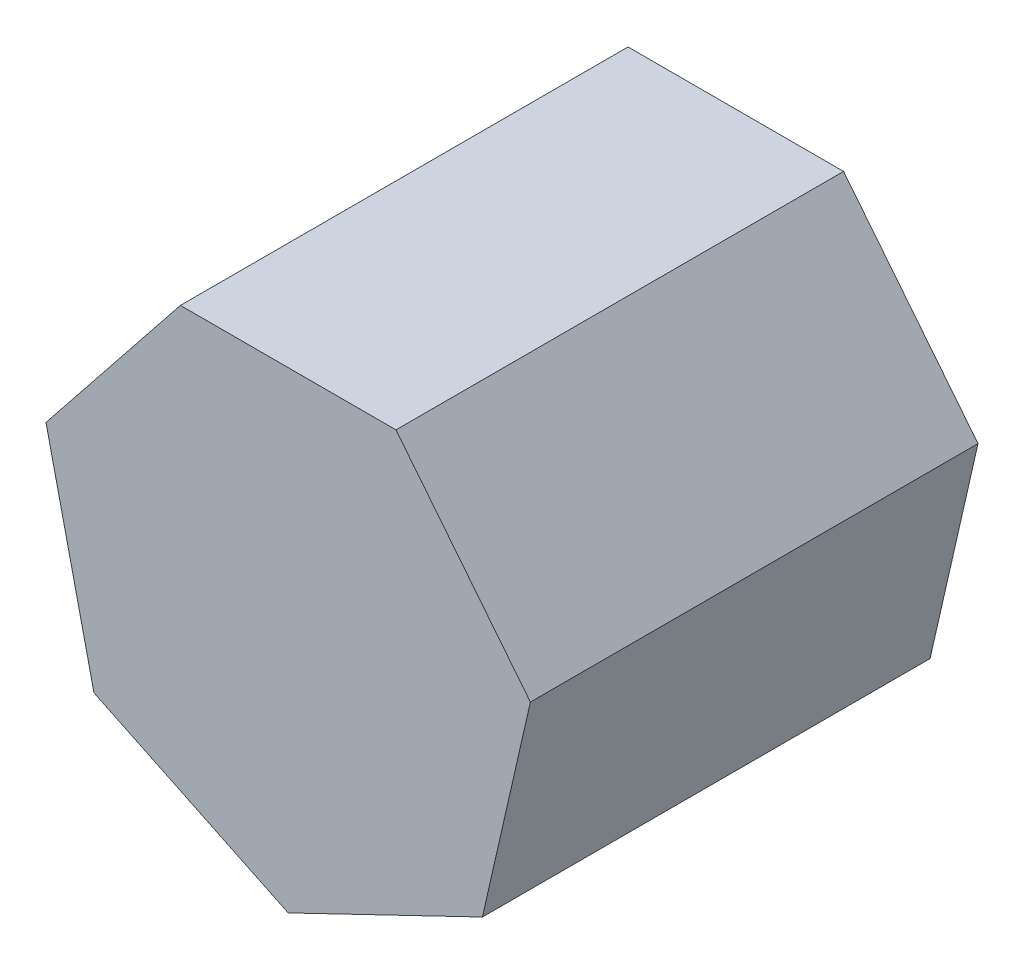
SolidWorks part; units mm, degrees
ref_plane "Front Plane" through (0, 0, 0) normal (0, 0, 1) x (1, 0, 0)
ref_plane "Top Plane" through (0, 0, 0) normal (0, 1, 0) x (1, 0, 0)
ref_plane "Right Plane" through (0, 0, 0) normal (1, 0, 0) x (0, 0, -1)
sketch "Sketch1" plane through (0, 0, 0) normal (0, 0, 1) x (1, 0, 0)
  line L1 (0, -110.9916) -> (86.7767, -69.2021)
  line L2 (86.7767, -69.2021) -> (108.2088, 24.698)
  line L3 (108.2088, 24.698) -> (48.1575, 100)
  line L4 (48.1575, 100) -> (-48.1575, 100)
  line L5 (-48.1575, 100) -> (-108.2088, 24.698)
  line L6 (-108.2088, 24.698) -> (-86.7767, -69.2021)
  line L7 (-86.7767, -69.2021) -> (0, -110.9916)
  circle A0 centre (0, 0) radius 100 construction
  dimension "D1" = 200
extrude "Boss-Extrude1" add sketch "Sketch1" along normal blind 200
sketch "Sketch2" plane through (-78.1831, 62.349, 0) normal (-0.7818, 0.6235, 0) x (0, 0, 1)
  text T0 "Andres" font "Century Gothic" height 20
extrude "Cut-Extrude1" cut sketch "Sketch2" against normal blind 1
sketch "Sketch4" plane through (-97.4928, -22.2521, 0) normal (-0.9749, -0.2225, 0) x (0, 0, 1)
  text T0 "Billy" font "Century Gothic" height 20
extrude "Cut-Extrude3" cut sketch "Sketch4" against normal blind 1
